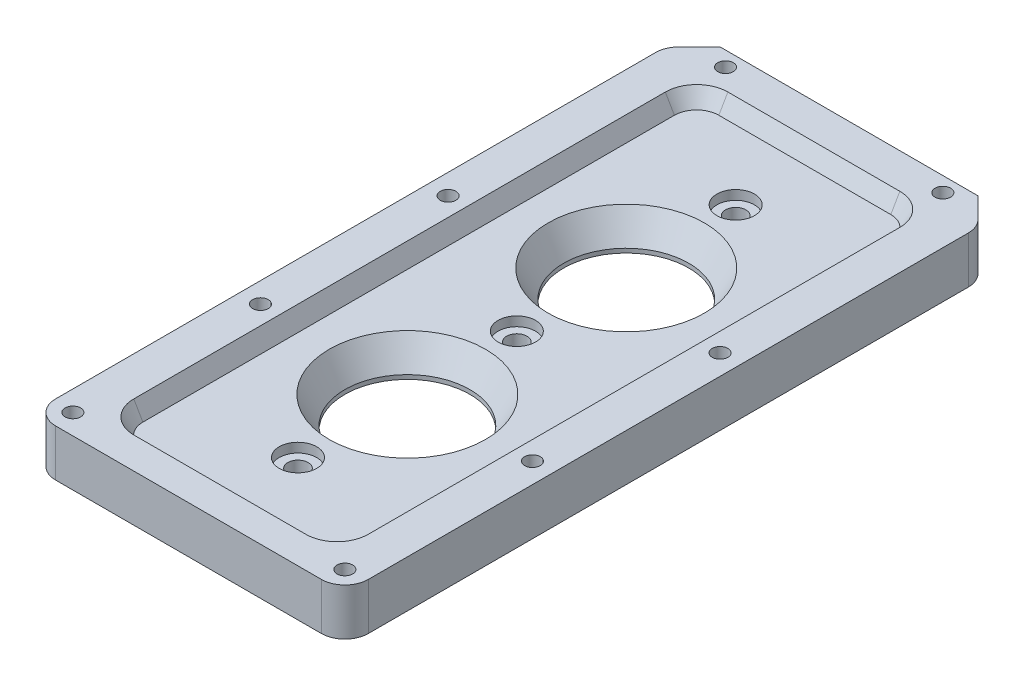
SolidWorks part; units mm, degrees
ref_plane "Front Plane" through (0, 0, 0) normal (0, 0, 1) x (1, 0, 0)
ref_plane "Top Plane" through (0, 0, 0) normal (0, 1, 0) x (1, 0, 0)
ref_plane "Right Plane" through (0, 0, 0) normal (1, 0, 0) x (0, 0, -1)
sketch "Sketch1" plane through (0, 0, 0) normal (0, 1, 0) x (1, 0, 0)
  line L2 (-42.5743, 39.6947) -> (-42.5743, -162.8053)
  line L3 (-42.5743, -162.8053) -> (57.4257, -162.8053)
  line L4 (57.4257, 39.6947) -> (57.4257, -162.8053)
  line L14 (-25.0743, 57.1947) -> (39.9257, 57.1947)
  line L17 (-25.0743, 57.1947) -> (39.9257, 57.1947)
  line L19 (-25.0743, 57.1947) -> (-42.5743, 39.6947)
  line L20 (39.9257, 57.1947) -> (57.4257, 39.6947)
  circle A1 centre (7.4257, 12.1947) radius 3.25
  circle A2 centre (7.4257, -57.8053) radius 3.25
  circle A3 centre (7.4257, -127.8053) radius 3.25
  circle A4 centre (-36.0743, -156.3053) radius 2.5
  circle A5 centre (50.9257, -156.3053) radius 2.5
  circle A6 centre (-36.0743, -96.3053) radius 2.5
  circle A7 centre (50.9257, -96.3053) radius 2.5
  circle A8 centre (-36.0743, -36.3053) radius 2.5
  circle A9 centre (50.9257, -36.3053) radius 2.5
  circle A10 centre (-27.3243, 43.6947) radius 2.5
  circle A11 centre (42.1757, 43.6947) radius 2.5
  circle A12 centre (7.4257, -22.8053) radius 20
  circle A13 centre (7.4257, -92.8053) radius 20
  point P15 (7.4257, -156.3053)
  point P32 (7.4257, 43.6947)
  point P39 (7.4257, 57.1947)
  dimension "D5" = 6.5
  dimension "D6" = 6.5
  dimension "D7" = 6.5
  dimension "D9" = 5
  dimension "D10" = 5
  dimension "D14" = 5
  dimension "D15" = 5
  dimension "D16" = 40
  dimension "D2" = 202.5
  dimension "D3" = 60
  dimension "D4" = 70
  dimension "D8" = 87
  dimension "D11" = 60
  dimension "D12" = 17.5
  dimension "D13" = 69.5
  dimension "D17" = 65
extrude "Boss-Extrude1" add sketch "Sketch1" along normal blind 15 contours L20 L14 L19 L2 L3 L4 A11 A10 A9 A8 A7 A6 A5 A4 A3 A2 A1 region at (7.4257, 0, 53.7301)
sketch "Sketch2" plane through (0, 15, 0) normal (0, 1, 0) x (1, 0, 0)
  circle A1 centre (7.4257, 12.1947) radius 6
  circle A2 centre (7.4257, -57.8053) radius 6
  circle A3 centre (7.4257, -127.8053) radius 6
  dimension "D1" = 12
  dimension "D2" = 12
  dimension "D3" = 12
extrude "Cut-Extrude1" cut sketch "Sketch2" against normal blind 8
fillet "Fillet1" radius 7.5 6 edges at (57.4257, 7.5, 162.8053) (-42.5743, 7.5, 162.8053) (-42.5743, 7.5, -39.6947) (-25.0743, 7.5, -57.1947) (57.4257, 7.5, -39.6947) (39.9257, 7.5, -57.1947)
sketch "Sketch4" plane through (0, 15, 0) normal (0, 1, 0) x (1, 0, 0)
  line L1 (-20.0743, -147.8053) -> (34.9257, -147.8053)
  line L2 (-25.0743, -142.8053) -> (-25.0743, 27.1947)
  line L3 (-20.0743, 32.1947) -> (34.9257, 32.1947)
  line L4 (39.9257, -142.8053) -> (39.9257, 27.1947)
  line L5 (-25.0743, -147.8053) -> (39.9257, 32.1947) construction
  line L6 (-25.0743, 32.1947) -> (39.9257, -147.8053) construction
  arc A0 (34.9257, -147.8053) -> (39.9257, -142.8053) centre (34.9257, -142.8053) ccw
  arc A1 (-20.0743, -147.8053) -> (-25.0743, -142.8053) centre (-20.0743, -142.8053) cw
  arc A2 (34.9257, 32.1947) -> (39.9257, 27.1947) centre (34.9257, 27.1947) cw
  arc A3 (-25.0743, 27.1947) -> (-20.0743, 32.1947) centre (-20.0743, 27.1947) cw
  point P0 (7.4257, -57.8053)
  dimension "D3" = 5
  dimension "D1" = 180
  dimension "D2" = 65
extrude "Cut-Extrude2" cut sketch "Sketch4" against normal blind 5
chamfer "Chamfer1" distance 5 angle 60 10 edges at (39.9257, 15, 57.8053) (38.4613, 15, -30.7303) (38.4613, 15, 146.3408) (7.4257, 15, -32.1947) (7.4257, 15, 147.8053) (-23.6098, 15, -30.7303) (-23.6098, 15, 146.3408) (-25.0743, 15, 57.8053) (7.4257, 10, 112.8053) (7.4257, 10, 42.8053) first distance on face at (7.4257, 15, 57.8053) first distance on face at (7.4257, 10, 42.8053)
sketch "Sketch5" plane through (0, 15, 0) normal (0, 1, 0) x (1, 0, 0)
  line L0 (-21.9677, 57.1947) -> (36.8191, 57.1947) construction
  line L1 (-33.8243, 65.9447) -> (48.6757, 65.9447)
  line L2 (-33.8243, 65.9447) -> (-33.8243, 48.4447)
  line L3 (-33.8243, 48.4447) -> (48.6757, 48.4447)
  line L4 (48.6757, 65.9447) -> (48.6757, 48.4447)
  line L5 (-33.8243, 65.9447) -> (48.6757, 48.4447) construction
  line L6 (-33.8243, 48.4447) -> (48.6757, 65.9447) construction
  line L7 (42.1224, 54.998) -> (55.229, 41.8914) construction
  point P0 (7.4257, 57.1947)
extrude "Cut-Extrude3" cut sketch "Sketch5" against normal up to surface (15 mm away) up to face at (7.4257, 0, 112.8053)
